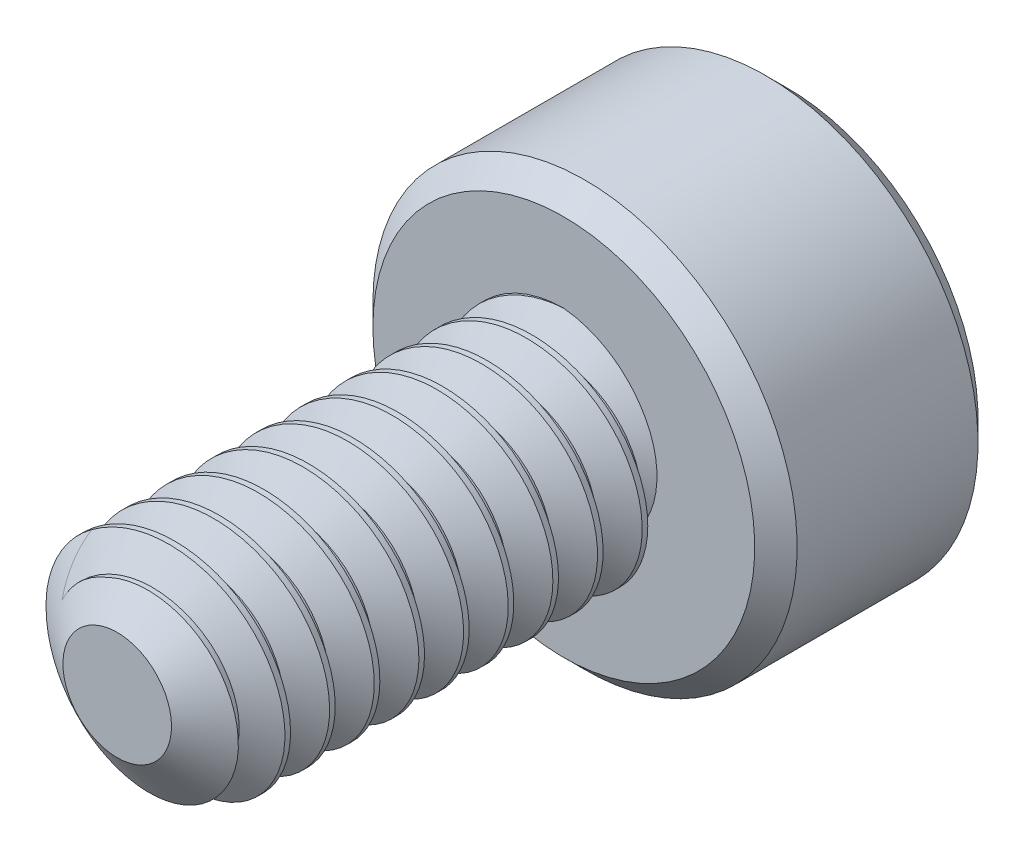
SolidWorks part; units mm, degrees
other "DetailItem1"
ref_plane "Front Plane" through (0, 0, 0) normal (0, 0, 1) x (1, 0, 0)
ref_plane "Top Plane" through (0, 0, 0) normal (0, 1, 0) x (1, 0, 0)
ref_plane "Right Plane" through (0, 0, 0) normal (1, 0, 0) x (0, 0, -1)
sketch "Sketch1" plane through (0, 0, 0) normal (0, 0, 1) x (1, 0, 0)
  circle A0 centre (0, 0) radius 1
  dimension "OD" = 2
extrude "Extrude1" add sketch "Sketch1" against normal blind 4
sketch "Sketch2" plane through (0, 0, 0) normal (0, 0, 1) x (1, 0, 0)
  circle A0 centre (0, 0) radius 1 construction
  circle A1 centre (0, 0) radius 1
curve "Helix/Spiral1" pitch 0.4 height 4.4 radius 1 centre (0, 0, 0) axis (0, 0, -1) start towards (0, 1, 0) parameters "pitch"=0.4
sketch "Sketch3" plane through (0, 0, 0) normal (1, 0, 0) x (0, 0, -1)
  line L0 (-0.35, 1) -> (-0.2, 0.7402)
  line L1 (-0.2, 0.7402) -> (-0.15, 0.7402)
  line L2 (-0.15, 0.7402) -> (0, 1)
  line L3 (-0.35, 1) -> (0, 1)
  line L4 (-0.175, 1) -> (-0.175, 0.7402) construction
  line L5 (-0.275, 0.8701) -> (-0.075, 0.8701) construction
  line L6 (0, 1) -> (0, -1) construction
  dimension "D1" = 0.05
  dimension "D2" = 0.2
  dimension "D3" = 60
sweep "Cut-Sweep1" cut profiles "Sketch3" path "Helix/Spiral1"
sketch "Sketch4" plane through (0, 0, 0) normal (1, 0, 0) x (0, 0, -1)
  line L0 (0.3598, 1) -> (0, 0.4862)
  line L1 (0, 0.4862) -> (0, 1)
  line L2 (0.3598, 1) -> (0, 1)
  line L3 (-0.35, 1) -> (0, 1) construction
  line L4 (0, 0) -> (7.0209, 0) construction
  dimension "D1" = 55
  dimension "D2" = 0.254
revolve "Cut-Revolve1" cut sketch "Sketch4" angle 360 about L4
sketch "Sketch6" plane through (0, 0, -4) normal (0, 0, -1) x (-1, 0, 0)
  circle A0 centre (0, 0) radius 1.9
  dimension "head dia" = 3.8
extrude "Extrude2" add sketch "Sketch6" along normal blind 2
sketch "Sketch7" plane through (0, 0, -6) normal (0, 0, -1) x (-1, 0, 0)
  line L1 (0, 0.866) -> (-0.75, 0.433)
  line L2 (-0.75, 0.433) -> (-0.75, -0.433)
  line L3 (-0.75, -0.433) -> (0, -0.866)
  line L4 (0, -0.866) -> (0.75, -0.433)
  line L5 (0.75, -0.433) -> (0.75, 0.433)
  line L6 (0.75, 0.433) -> (0, 0.866)
  circle A0 centre (0, 0) radius 0.75 construction
  dimension "hex dia" = 1.5
extrude "Cut-Extrude1" cut sketch "Sketch7" against normal blind 1.125
sketch "Sketch8" plane through (0, 0, -6) normal (0, 0, -1) x (-1, 0, 0)
  circle A0 centre (0, 0) radius 0.866
extrude "Cut-Extrude2" cut sketch "Sketch8" against normal through all draft 45
chamfer "Chamfer1" distance 0.19 angle 45 2 edges at (-1.9, 0, -6) (-1.9, 0, -4)
sketch "Sketch10" plane through (0, 0, -4) normal (0, 0, 1) x (1, 0, 0)
  circle A1 centre (0, 0) radius 1
  circle A2 centre (0, 0) radius 1
  dimension "D1" = 0
ref_plane "Plane1" through (0, 0, 0) normal (0, 0, 1) x (1, 0, 0)
extrude "partial thread" [suppressed] add sketch "Sketch10" along normal up to surface (36 mm away) separate body up to plane "Plane1"
chamfer "Chamfer2" [suppressed] distance 0.04 angle 45
combine bodies "Combine1" [suppressed] operation type add bodies to combine 107 108
sketch "Sketch9" plane through (0, 0, 0) normal (1, 0, 0) x (0, 0, -1)
  line L0 (0, 1) -> (0, -1) construction
  line L1 (1, 1) -> (1, -1) construction
  dimension "D1" = 1
equation "\"D3@Helix/Spiral1\" = \"screw length@Extrude1\"+\"pitch@Helix/Spiral1\""
equation "\"D1@Sketch3\" = \"pitch@Helix/Spiral1\"*.125"
equation "\"D2@Sketch3\" = \"pitch@Helix/Spiral1\"*.5"
equation "\"D1@Cut-Extrude1\" = \"hex dia@Sketch7\"*.75"
equation "\"D1@Chamfer1\" = \"head dia@Sketch6\"*.05"
equation "\"D1@Sketch9\" = \"pitch@Helix/Spiral1\"*2.5"
equation "\"D1@Chamfer2\"=\"OD@Sketch1\"*.02"
